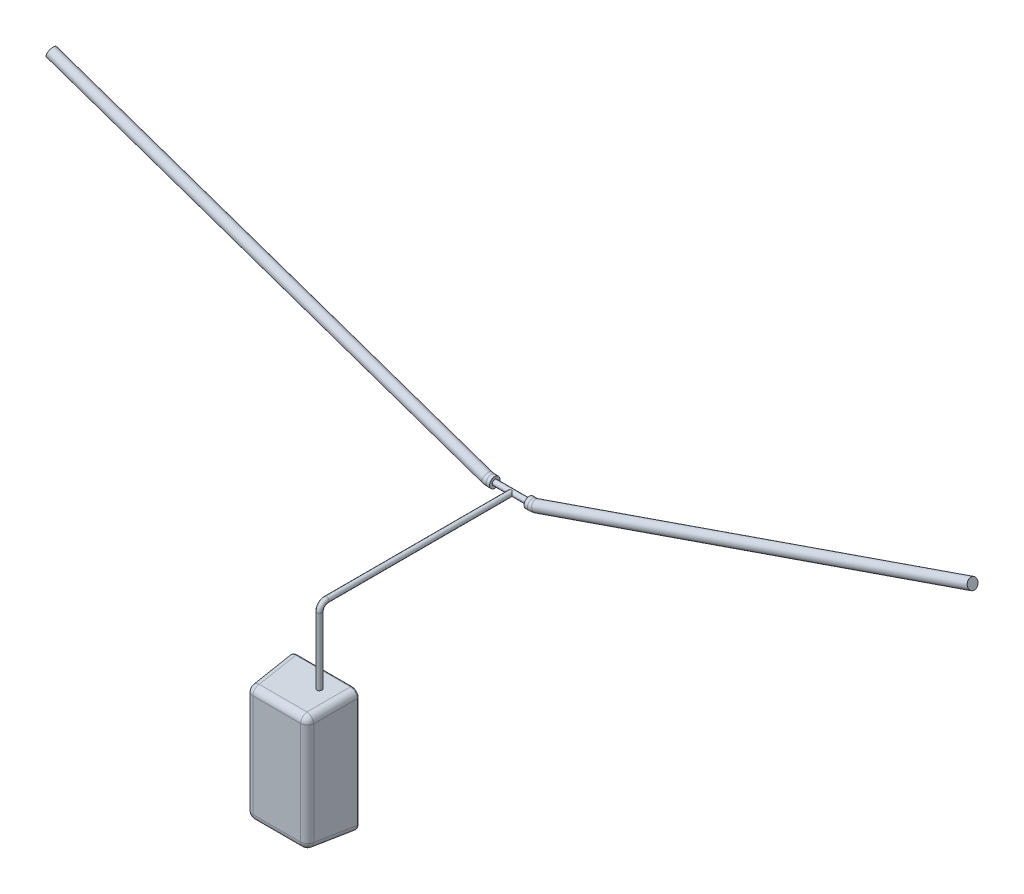
SolidWorks part; units mm, degrees
ref_plane "Front" through (0, 0, 0) normal (0, 0, 1) x (1, 0, 0)
ref_plane "Top" through (0, 0, 0) normal (0, 1, 0) x (1, 0, 0)
ref_plane "Right" through (0, 0, 0) normal (1, 0, 0) x (0, 0, -1)
sketch "Sketch1" plane through (0, 0, 0) normal (0, 0, 1) x (1, 0, 0)
  line L1 (-127, 228.6) -> (127, 228.6)
  line L2 (-127, 228.6) -> (-127, -228.6)
  line L3 (-127, -228.6) -> (127, -228.6)
  line L4 (127, 228.6) -> (127, -228.6)
  line L5 (-127, 228.6) -> (127, -228.6) construction
  line L6 (-127, -228.6) -> (127, 228.6) construction
  point P0 (0, 0)
  dimension "D1" = 254
  dimension "D2" = 457.2
extrude "Boss-Extrude1" add sketch "Sketch1" along normal blind 177.8 draft 5
fillet "Fillet1" radius 25.4 4 edges at (119.2223, -220.8223, 88.9) (-119.2223, -220.8223, 88.9) (119.2223, 220.8223, 88.9) (-119.2223, 220.8223, 88.9)
fillet "Fillet2" radius 25.4 8 edges at (-104.045, -205.645, 177.8) (-111.4445, 0, 177.8) (-104.045, 205.645, 177.8) (0, 213.0445, 177.8) (104.045, 205.645, 177.8) (111.4445, 0, 177.8) (104.045, -205.645, 177.8) (0, -213.0445, 177.8)
fillet "Fillet3" radius 6.35 8 edges at (119.6004, -221.2004, 0) (0, -228.6, 0) (-119.6004, -221.2004, 0) (-127, 0, 0) (-119.6004, 221.2004, 0) (0, 228.6, 0) (119.6004, 221.2004, 0) (127, 0, 0)
sketch "Sketch2" plane through (0, 0, 0) normal (0, 1, 0) x (1, 0, 0)
  line L0 (0, 0) -> (0, -69.85) construction
  line L1 (0, -69.85) -> (-76.2, -69.85) construction
  line L2 (0, -69.85) -> (25.4, -69.85) construction
  circle A0 centre (-76.2, -69.85) radius 3.175
  circle A1 centre (25.4, -69.85) radius 9.525
  dimension "D3" = 6.35
  dimension "D4" = 19.05
  dimension "D1" = 25.4
  dimension "D2" = 76.2
  dimension "D5" = 69.85
extrude "Boss-Extrude2" add sketch "Sketch2" against normal blind 279.4
sketch "Sketch3" plane through (0, 0, 0) normal (0, 1, 0) x (1, 0, 0)
  line L0 (0, 0) -> (0, -64.4508) construction
  line L1 (0, -64.4508) -> (44.45, -64.4508) construction
  circle A0 centre (44.45, -64.4508) radius 9.525
  dimension "D2" = 19.05
  dimension "D1" = 44.45
  dimension "D3" = 64.4508
extrude "Boss-Extrude3" add sketch "Sketch3" along normal blind 457.2
ref_axis "Axis1" through (44.45, 457.2, 64.4508) along (0, -1, 0)
ref_plane "Plane1" through (0, 0, 64.4508) normal (0, 0, -1) x (-1, 0, 0)
ref_plane "Plane2" through (44.45, 0, 0) normal (1, 0, 0) x (0, -1, 0)
sketch "Sketch5" plane through (44.45, 0, 0) normal (1, 0, 0) x (0, -1, 0)
  line L0 (-457.2, -64.4508) -> (-469.9, -64.4508)
  line L1 (-457.2, -54.9258) -> (-457.2, -73.9758) construction
  line L2 (-495.3, -39.0508) -> (-495.3, 646.7492)
  arc A0 (-469.9, -64.4508) -> (-495.3, -39.0508) centre (-469.9, -39.0508) cw
  dimension "D2" = 25.4
  dimension "D1" = 12.7
  dimension "D3" = 685.8
sketch "Sketch6" plane through (0, 457.2, 0) normal (0, 1, 0) x (1, 0, 0)
  circle A1 centre (44.45, -64.4508) radius 9.525
  circle A2 centre (44.45, -64.4508) radius 9.525
  dimension "D1" = 0
sweep "Sweep1" add profiles "Sketch6" path "Sketch5"
sketch "Sketch7" plane through (44.45, 0, 0) normal (1, 0, 0) x (0, -1, 0)
  line L0 (-485.775, 646.7492) -> (-504.825, 646.7492) construction
  circle A0 centre (-495.3, 646.7492) radius 9.525
extrude "Boss-Extrude4" add sketch "Sketch7" along normal mid plane 127
ref_axis "Axis2" through (107.95, 495.3, -646.7492) along (-1, 0, 0)
ref_plane "Plane3" through (0, 0, -646.7492) normal (0, 0, -1) x (-1, 0, 0)
sketch "Sketch8" plane through (0, 0, -646.7492) normal (0, 0, -1) x (-1, 0, 0)
  line L0 (19.05, 495.3) -> (31.75, 495.3)
  line L1 (19.05, 485.775) -> (19.05, 504.825) construction
  line L2 (48.3419, 498.0859) -> (1657.35, 1054.1)
  line L3 (1657.35, 1054.1) -> (1657.35, 495.3) construction
  line L4 (1657.35, 495.3) -> (31.75, 495.3) construction
  arc A0 (31.75, 495.3) -> (48.3419, 498.0859) centre (31.75, 546.1) ccw
  point P7 (1897.8801, 495.3)
  dimension "D1" = 50.8
  dimension "D2" = 1625.6
  dimension "D3" = 558.8
  dimension "D6" = 12.7
sketch "Sketch9" plane through (-19.05, 0, 0) normal (-1, 0, 0) x (0, 0, 1)
  circle A1 centre (-646.7492, 495.3) radius 19.05
  dimension "D1" = 38.1
sweep "Sweep3" add profiles "Sketch9" path "Sketch8"
mirror "Mirror1" about plane through (44.45, 0, 0) normal (1, 0, 0) of "Sweep3"
